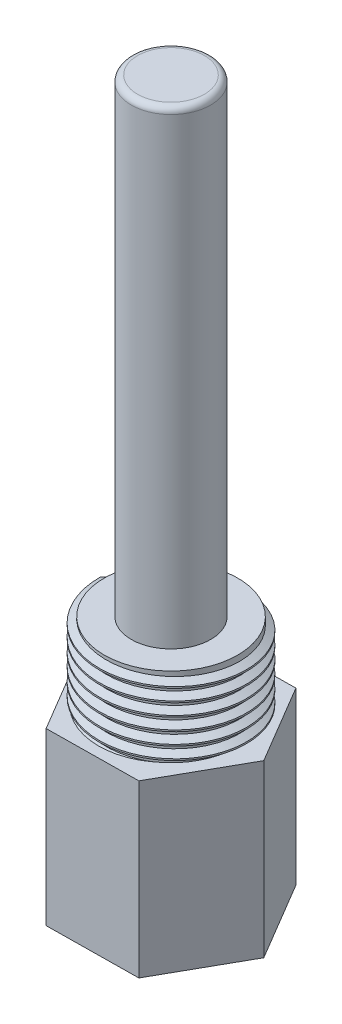
SolidWorks part; units mm, degrees
material "AISI 304"
ref_plane "Alzado" through (0, 0, 0) normal (0, 0, 1) x (1, 0, 0)
ref_plane "Planta" through (0, 0, 0) normal (0, 1, 0) x (1, 0, 0)
ref_plane "Vista lateral" through (0, 0, 0) normal (1, 0, 0) x (0, 0, -1)
sketch "Croquis1" plane through (0, 0, 0) normal (0, 1, 0) x (1, 0, 0)
  line L1 (-7.4786, 12.6145) -> (-14.6637, -0.1694)
  line L2 (-14.6637, -0.1694) -> (-7.1852, -12.7839)
  line L3 (-7.1852, -12.7839) -> (7.4786, -12.6145)
  line L4 (7.4786, -12.6145) -> (14.6637, 0.1694)
  line L5 (14.6637, 0.1694) -> (7.1852, 12.7839)
  line L6 (7.1852, 12.7839) -> (-7.4786, 12.6145)
  circle A0 centre (0, 0) radius 12.7 construction
  dimension "D1" = 25.4
extrude "Saliente-Extruir1" add sketch "Croquis1" along normal blind 27.3
sketch "Croquis6" plane through (0, 27.3, 0) normal (0, 1, 0) x (1, 0, 0)
  circle A0 centre (0, 0) radius 10.67
  dimension "D1" = 21.34
extrude "Saliente-Extruir3" add sketch "Croquis6" along normal blind 12.7
sketch "Croquis7" plane through (0, 40, 0) normal (0, 1, 0) x (1, 0, 0)
  circle A0 centre (0, 0) radius 6.35
extrude "Saliente-Extruir4" add sketch "Croquis7" along normal blind 75
fillet "Redondeo2" radius 1 1 edges at (0, 115, 6.35)
sketch "Croquis8" plane through (0, 0, 0) normal (0, -1, 0) x (-1, 0, 0)
  circle A0 centre (0, 0) radius 3.175
  dimension "D1" = 6.35
extrude "Cortar-Extruir1" cut sketch "Croquis8" against normal blind 113
sketch "Croquis12" plane through (0, 0, 0) normal (0, -1, 0) x (1, 0, 0)
  circle A0 centre (0, 0) radius 9.525
  dimension "D1" = 19.05
extrude "Cortar-Extruir2" cut sketch "Croquis12" against normal blind 24
thread "Rosca1" pitch 2 start angle 0, offset 0, length 0, pitch 2, diameter 19.05
ref_plane "Plano1" through (9.525, 0, 0) normal (0, 0, 1) x (1, 0, 0)
sketch "Perfil de rosca1" plane through (9.525, 0, 0) normal (0, 0, 1) x (1, 0, 0)
  line L0 (0, 0) -> (0, 2) construction
  line L1 (0, 0) -> (1.0825, 0.625)
  line L2 (1.0825, 0.625) -> (1.0825, 0.875)
  line L3 (1.0825, 0.875) -> (0, 1.5)
  line L4 (1.0825, 0.75) -> (0, 0.75) construction
  line L11 (0, 0) -> (0, 1.5)
  point P2 (0, 0)
  dimension "Pitch" = 2
  dimension "Profile_Angle" = 60
  dimension "Profile_Land" = 0.25
  dimension "Profile_Height" = 1.0825
thread "Rosca2" start angle 1.9, offset 0, length 12.7, pitch 2, diameter 21.34
ref_plane "Plano5" through (-10.6641, 40, -0.3538) normal (-0.0332, 0, 0.9995) x (-0.9995, 0, -0.0332)
sketch "Perfil de rosca5" plane through (-10.6641, 40, -0.3538) normal (-0.0332, 0, 0.9995) x (-0.9995, 0, -0.0332)
  line L0 (0, 0) -> (0, 2) construction
  line L1 (0, 0) -> (1.0825, 0.625)
  line L2 (1.0825, 0.625) -> (1.0825, 0.875)
  line L3 (1.0825, 0.875) -> (0, 1.5)
  line L4 (1.0825, 0.75) -> (0, 0.75) construction
  line L11 (0, 0) -> (0, 1.5)
  point P2 (0, 0)
  dimension "Pitch" = 2
  dimension "Profile_Angle" = 60
  dimension "Profile_Land" = 0.25
  dimension "Profile_Height" = 1.0825
